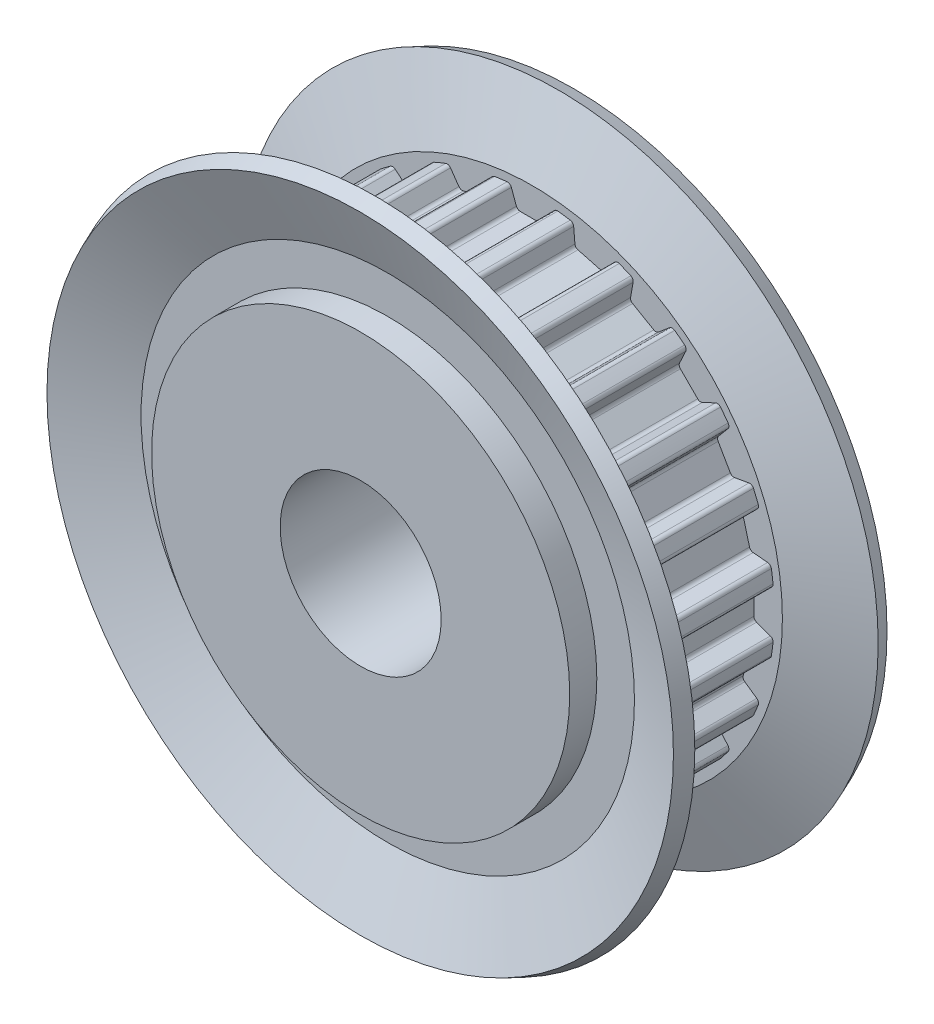
SolidWorks part; units mm, degrees
ref_plane "Front Plane" through (0, 0, 0) normal (0, 0, 1) x (1, 0, 0)
ref_plane "Top Plane" through (0, 0, 0) normal (0, 1, 0) x (1, 0, 0)
ref_plane "Right Plane" through (0, 0, 0) normal (1, 0, 0) x (0, 0, -1)
ref_axis "Axis1" through (0, 0, 55) along (0, 0, -1)
sketch "SketchRevolveGearBelt01" plane through (0, 0, 0) normal (1, 0, 0) x (0, 0, -1)
  line L0 (0, 0) -> (1, 0) construction
  line L1 (3.302, 0) -> (3.302, 6.4917)
  line L2 (3.302, 6.4917) -> (2.4606, 6.4917)
  line L3 (2.4606, 6.4917) -> (2.4606, 7.6606)
  line L4 (2.4606, 7.6606) -> (3.3162, 9.7263)
  line L5 (3.3162, 9.7263) -> (2.8469, 9.9207)
  line L6 (2.8469, 9.9207) -> (2.032, 7.7617)
  line L7 (2.032, 7.7617) -> (2.032, 7.5117)
  line L8 (2.032, 7.5117) -> (-2.032, 7.5117)
  line L9 (-2.032, 7.5117) -> (-2.032, 7.7617)
  line L10 (-2.032, 7.7617) -> (-2.8469, 9.9207)
  line L11 (-2.8469, 9.9207) -> (-3.3162, 9.7263)
  line L12 (-3.3162, 9.7263) -> (-2.4606, 7.6606)
  line L13 (-2.4606, 7.6606) -> (-2.4606, 6.4917)
  line L14 (-2.4606, 6.4917) -> (-3.302, 6.4917)
  line L15 (-3.302, 6.4917) -> (-3.302, 0)
  line L16 (-3.302, 0) -> (3.302, 0)
  dimension "GearBeltSide1" = 3.302
  dimension "GearBeltFlange1OutsideWidth" = 2.4606
  dimension "GearBeltFlange1OutsideLength" = 1.169
  dimension "GearBeltFlange1X" = 0.8556
  dimension "GearBeltFlange1Y" = 2.0656
  dimension "GearBeltFlangeThickness" = 1.821
  dimension "GearBeltToothWidth1" = 2.032
  dimension "GearBeltFlangeInside" = 0.25
  dimension "GearBeltOutsideDiameter" = 7.5117
  dimension "GearBeltToothWidth2" = 2.032
  dimension "GearBeltFlange2X" = 0.8556
  dimension "GearBeltFlange2OutsideWidth" = 2.4606
revolve "GearBelt01" add sketch "SketchRevolveGearBelt01" angle 360 about L0
sketch "SketchToothGearBelt01" plane through (0, 0, 0) normal (0, 0, 1) x (1, 0, 0)
  line L0 (-0.6545, 7.3874) -> (-0.499, 6.9602)
  line L1 (-0.3797, 6.8767) -> (0.3797, 6.8767)
  line L2 (0.499, 6.9602) -> (0.6545, 7.3874)
  line L3 (0.7872, 7.4703) -> (0, 10.0103)
  line L4 (0, 10.0103) -> (-0.7872, 7.4703)
  arc A0 (-0.7872, 7.4703) -> (-0.6545, 7.3874) centre (-0.7739, 7.344) cw
  arc A1 (-0.499, 6.9602) -> (-0.3797, 6.8767) centre (-0.3797, 7.0037) ccw
  arc A2 (0.3797, 6.8767) -> (0.499, 6.9602) centre (0.3797, 7.0037) ccw
  arc A3 (0.6545, 7.3874) -> (0.7872, 7.4703) centre (0.7739, 7.344) cw
  dimension "GearBeltToothR1" = 0.254
  dimension "GearBeltToothR2" = 0.254
  dimension "GearBeltToothX1" = 0.1555
  dimension "GearBeltToothY1" = 0.4272
  dimension "GearBeltToothRootX" = 6.8767
  dimension "GearBeltToothRootY" = 6.8767
  dimension "GearBeltToothX2" = 0.1555
  dimension "GearBeltToothY2" = 0.4272
  dimension "GearBeltToothCapX1" = 0.7872
  dimension "GearBeltToothCapY1" = 2.54
  dimension "GearBeltToothCapX2" = 0.7872
  dimension "GearBeltToothCapY2" = 2.54
extrude "ToothExtrudeCutGearBelt01" cut sketch "SketchToothGearBelt01" against normal blind 2.032 and the other way blind 2.032
pattern_circular "PatternGearBelt01" count 24 every 15 about axis through (0, 0, 55) along (0, 0, -1) of "ToothExtrudeCutGearBelt01"
sketch "BoreRevolveSketch" plane through (0, 0, 0) normal (1, 0, 0) x (0, 0, -1)
  line L0 (0, 0) -> (1, 0) construction
  line L1 (-3.302, 0) -> (3.302, 0)
  line L2 (3.302, 0) -> (3.302, 2.5)
  line L3 (3.302, 2.5) -> (-3.302, 2.5)
  line L4 (-3.302, 2.5) -> (-3.302, 0)
  dimension "BoreSide1" = 3.302
  dimension "TaperSide1" = 2.5
  dimension "BoreSide2" = 3.302
  dimension "TaperSide2" = 2.5
revolve "BoreRevolveCut" cut sketch "BoreRevolveSketch" angle 360 about L0
sketch "AuxiliarySketchGearBelt01" plane through (0, 0, 0) normal (0, 0, 1) x (1, 0, 0)
  circle A0 centre (0, 0) radius 7.7617 construction
  dimension "PitchDiameter" = 15.5233
